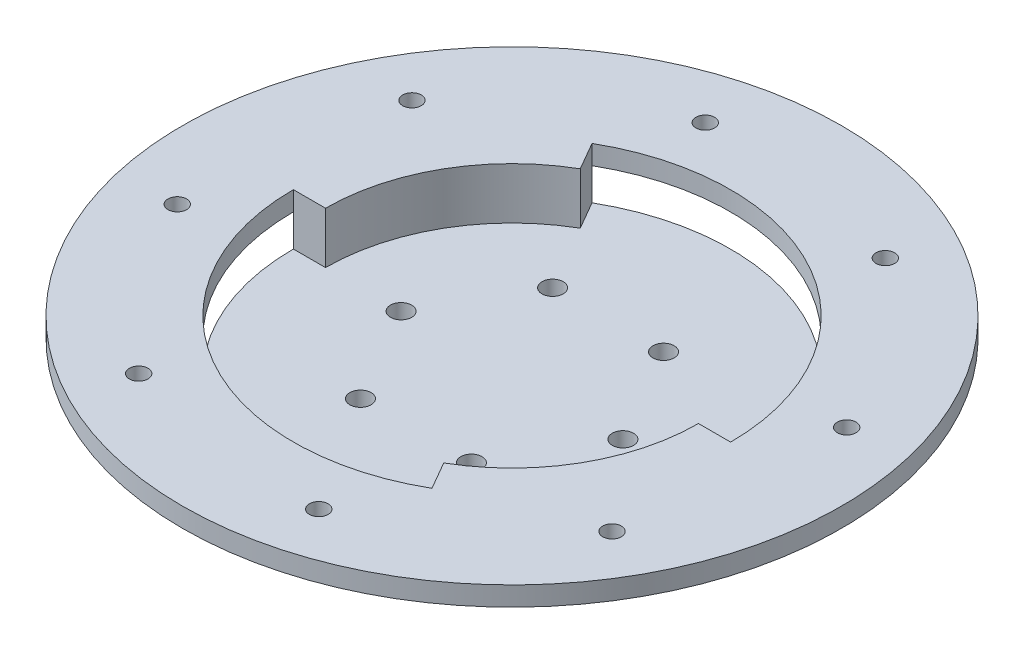
SolidWorks part; units mm, degrees
ref_plane "前视基准面" through (0, 0, 0) normal (0, 0, 1) x (1, 0, 0)
ref_plane "上视基准面" through (0, 0, 0) normal (0, 1, 0) x (1, 0, 0)
ref_plane "右视基准面" through (0, 0, 0) normal (1, 0, 0) x (0, 0, -1)
sketch "草图1" plane through (0, 0, 0) normal (0, 1, 0) x (1, 0, 0)
  circle A0 centre (0, 0) radius 34
extrude "凸台-拉伸2" add sketch "草图1" along normal blind 5
sketch "草图2" plane through (0, 5, 0) normal (0, 1, 0) x (1, 0, 0)
  line L0 (-34, 0) -> (-29, 0)
  line L1 (-14.5, 25.1147) -> (-17, 29.4449)
  line L2 (29, 0) -> (34, 0)
  line L3 (14.5, -25.1147) -> (17, -29.4449)
  arc A0 (-14.5, 25.1147) -> (-29, 0) centre (0, 0) ccw
  arc A1 (-17, 29.4449) -> (-34, 0) centre (0, 0) ccw
  arc A2 (14.5, -25.1147) -> (29, 0) centre (0, 0) ccw
  arc A3 (17, -29.4449) -> (34, 0) centre (0, 0) ccw
  dimension "D1" = 60
  dimension "D2" = 60
extrude "凸台-拉伸3" add sketch "草图2" along normal blind 8
sketch "草图3" plane through (0, 13, 0) normal (0, 1, 0) x (1, 0, 0)
  circle A0 centre (0, 0) radius 34
  circle A1 centre (0, 0) radius 46.25
extrude "凸台-拉伸4" add sketch "草图3" against normal blind 3
sketch "草图4" plane through (0, 13, 0) normal (0, 1, 0) x (1, 0, 0)
  circle A0 centre (0, 0) radius 51.25
  circle A1 centre (0, 0) radius 46.25
extrude "凸台-拉伸5" add sketch "草图4" along normal blind 27.3 and the other way blind 3
sketch "草图5" plane through (0, 40.3, 0) normal (0, 1, 0) x (1, 0, 0)
  circle A0 centre (0, 0) radius 58
  circle A1 centre (0, 0) radius 51.25
extrude "凸台-拉伸6" add sketch "草图5" against normal blind 5
sketch "草图6" plane through (0, 0, 0) normal (0, -1, 0) x (1, 0, 0)
  point P4 (8.625, -14.9389)
hole_wizard "M4 螺纹孔1" positions "草图6" profile "草图7" tap size "M4" standard "DIN" end condition through all
sketch "草图7" plane through (8.625, 0, -14.9389) normal (1, 0, 0) x (0, 0, -1)
  line L0 (0, 0) -> (0, 40.3)
  line L1 (0, 40.3) -> (1.65, 40.3)
  line L2 (1.65, 40.3) -> (1.65, 0.375)
  line L3 (1.65, 0.375) -> (2.025, 0)
  line L5 (2.025, 0) -> (0, 0)
  line L6 (-1.65, 0.375) -> (-2.025, 0) construction
  line L11 (0, -6.35) -> (0, 107.95) construction
  dimension "通孔螺纹孔钻头直径" = 3.3
  dimension "通孔螺纹孔钻头深度" = 40.3
  dimension "近端锥形沉头孔直径" = 4.05
  dimension "近端锥形沉头孔角度" = 90
cosmetic thread "孔螺纹线1" parameters "D2"=4
pattern_circular "阵列(圆周)1" count 6 every 60 about axis through (0, 0, 0) along (0, 1, 0) of "M4 螺纹孔1"
sketch "草图8" plane through (0, 10, 0) normal (0, -1, 0) x (1, 0, 0)
  point P10 (36.8061, 21.25)
  dimension "D1" = 42.5
hole_wizard "M3.5 螺纹孔1" positions "草图8" profile "草图9" tap size "M3.5" standard "DIN" end condition through all
sketch "草图9" plane through (36.8061, 10, 21.25) normal (1, 0, 0) x (0, 0, -1)
  line L0 (0, 0) -> (0, 30.3)
  line L1 (0, 30.3) -> (1.45, 30.3)
  line L2 (1.45, 30.3) -> (1.45, 0.325)
  line L3 (1.45, 0.325) -> (1.775, 0)
  line L5 (1.775, 0) -> (0, 0)
  line L6 (-1.45, 0.325) -> (-1.775, 0) construction
  line L11 (0, -6.35) -> (0, 107.95) construction
  dimension "通孔螺纹孔钻头直径" = 2.9
  dimension "通孔螺纹孔钻头深度" = 30.3
  dimension "近端锥形沉头孔直径" = 3.55
  dimension "近端锥形沉头孔角度" = 90
cosmetic thread "孔螺纹线2" parameters "D2"=3.5
pattern_circular "阵列(圆周)2" count 8 every 45 about axis through (0, 0, 0) along (0, 1, 0) of "M3.5 螺纹孔1"
sketch "草图10" plane through (0, 40.3, 0) normal (0, 1, 0) x (1, 0, 0)
  circle A0 centre (0, 0) radius 58
extrude "切除-拉伸1" cut sketch "草图10" against normal blind 27.3
